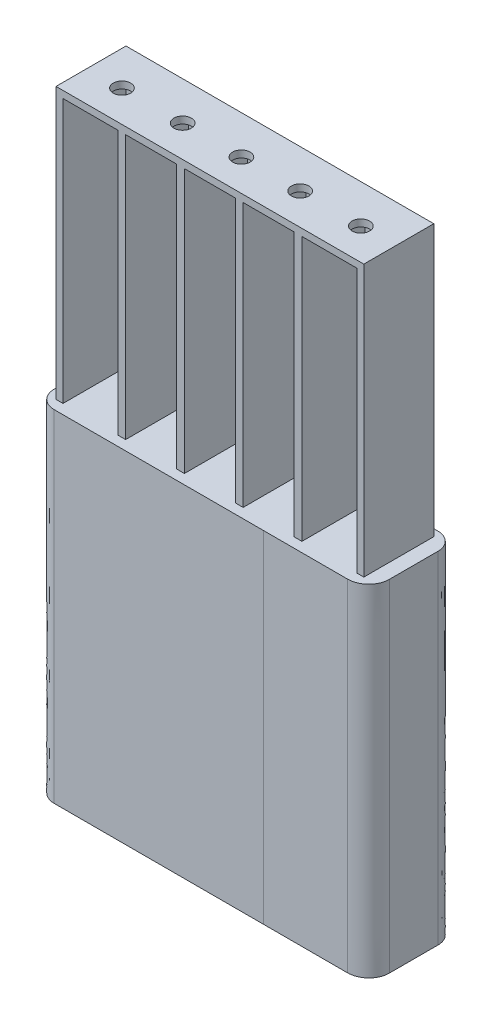
SolidWorks part; units mm, degrees
ref_plane "Front Plane" through (0, 0, 0) normal (0, 0, 1) x (1, 0, 0)
ref_plane "Top Plane" through (0, 0, 0) normal (0, 1, 0) x (1, 0, 0)
ref_plane "Right Plane" through (0, 0, 0) normal (1, 0, 0) x (0, 0, -1)
ref_plane "Plane1" through (0, 10, 0) normal (0, 1, 0) x (1, 0, 0)
sketch "Sketch1" plane through (0, 0, 0) normal (0, 0, 1) x (1, 0, 0)
  line L1 (-44, -87.5) -> (44, -87.5)
  line L2 (-44, -87.5) -> (-44, 87.5)
  line L3 (-44, 87.5) -> (44, 87.5)
  line L4 (44, -87.5) -> (44, 87.5)
  line L5 (-44, -87.5) -> (44, 87.5) construction
  line L6 (-44, 87.5) -> (44, -87.5) construction
  point P0 (0, 0)
  dimension "D1" = 88
  dimension "D2" = 175
extrude "Boss-Extrude1" add sketch "Sketch1" along normal blind 2
sketch "Sketch2" plane through (0, 0, 2) normal (0, 0, 1) x (1, 0, 0)
  line L4 (44, -87.5) -> (44, 87.5)
  line L5 (44, 87.5) -> (-44, 87.5)
  line L6 (-44, 87.5) -> (-44, -87.5)
  line L7 (-44, -87.5) -> (44, -87.5)
  line L8 (44, -87.5) -> (44, 87.5)
  line L9 (44, 87.5) -> (-44, 87.5)
  line L10 (-44, 87.5) -> (-44, -87.5)
  line L11 (-44, -87.5) -> (44, -87.5)
  dimension "D1" = 0
extrude "Extrude-Thin1" add sketch "Sketch2" along normal blind 18 thin thin type one direction reverse wall 2
sketch "Sketch3" plane through (0, 0, 2) normal (0, 0, 1) x (1, 0, 0)
  line L0 (-25.2, 85.5) -> (-25.2, -85.5)
  line L1 (42, 85.5) -> (-42, 85.5) construction
  line L2 (-42, -85.5) -> (42, -85.5) construction
  line L3 (-8.4, 85.5) -> (-8.4, -85.5)
  line L4 (42, 85.5) -> (-42, 85.5) construction
  line L5 (25.2, 85.5) -> (25.2, -85.5)
  line L6 (8.4, 85.5) -> (8.4, -85.5)
  line L7 (-42, -85.5) -> (42, -85.5) construction
  line L8 (-42, 85.5) -> (-42, -85.5) construction
  line L9 (42, -85.5) -> (42, 85.5) construction
  dimension "D1" = 16.8
  dimension "D2" = 16.8
  dimension "D3" = 16.8
  dimension "D4" = 16.8
  dimension "D5" = 16.8
extrude "Extrude-Thin2" add sketch "Sketch3" along normal blind 18 thin thin type mid plane wall 2.2
sketch "Sketch4" plane through (0, 87.5, 0) normal (0, 1, 0) x (1, 0, 0)
  line L0 (26.3, -20) -> (26.3, -2) construction
  line L1 (26.3, -2) -> (42, -2) construction
  line L2 (42, -2) -> (42, -20) construction
  line L3 (42, -20) -> (26.3, -20) construction
  line L4 (9.5, -20) -> (9.5, -2) construction
  line L5 (9.5, -2) -> (24.1, -2) construction
  line L6 (24.1, -2) -> (24.1, -20) construction
  line L7 (24.1, -20) -> (9.5, -20) construction
  line L8 (-7.3, -2) -> (7.3, -2) construction
  line L9 (7.3, -2) -> (7.3, -20) construction
  line L10 (7.3, -20) -> (-7.3, -20) construction
  line L11 (-7.3, -20) -> (-7.3, -2) construction
  line L12 (-24.1, -2) -> (-9.5, -2) construction
  line L13 (-9.5, -2) -> (-9.5, -20) construction
  line L14 (-9.5, -20) -> (-24.1, -20) construction
  line L15 (-24.1, -20) -> (-24.1, -2) construction
  line L16 (-42, -2) -> (-26.3, -2) construction
  line L17 (-26.3, -2) -> (-26.3, -20) construction
  line L18 (-26.3, -20) -> (-42, -20) construction
  line L19 (-42, -20) -> (-42, -2) construction
  line L20 (26.3, -20) -> (26.3, -2) construction
  line L21 (26.3, -2) -> (42, -2) construction
  line L22 (42, -2) -> (42, -20) construction
  line L23 (42, -20) -> (26.3, -20) construction
  line L24 (9.5, -20) -> (9.5, -2) construction
  line L25 (9.5, -2) -> (24.1, -2) construction
  line L26 (24.1, -2) -> (24.1, -20) construction
  line L27 (24.1, -20) -> (9.5, -20) construction
  line L28 (-7.3, -2) -> (7.3, -2) construction
  line L29 (7.3, -2) -> (7.3, -20) construction
  line L30 (7.3, -20) -> (-7.3, -20) construction
  line L31 (-7.3, -20) -> (-7.3, -2) construction
  line L32 (-24.1, -2) -> (-9.5, -2) construction
  line L33 (-9.5, -2) -> (-9.5, -20) construction
  line L34 (-9.5, -20) -> (-24.1, -20) construction
  line L35 (-24.1, -20) -> (-24.1, -2) construction
  line L36 (-42, -2) -> (-26.3, -2) construction
  line L37 (-26.3, -2) -> (-26.3, -20) construction
  line L38 (-26.3, -20) -> (-42, -20) construction
  line L39 (-42, -20) -> (-42, -2) construction
  line L40 (42, -11) -> (-42, -11) construction
  line L41 (-16.8, -20) -> (-16.8, -2) construction
  line L42 (-34.15, -20) -> (-34.15, -2) construction
  line L43 (0, -20) -> (0, -2) construction
  line L44 (16.8, -20) -> (16.8, -2) construction
  line L45 (34.15, -20) -> (34.15, -2) construction
  point P26 (34.15, -11)
  point P28 (16.8, -11)
  point P30 (0, -11)
  point P31 (-16.8, -11)
  point P34 (-34.15, -11)
hole_wizard "Ø5.0mm Dowel Hole3" positions "Sketch5" profile "Sketch6" hole size "Ø5.0" standard "BSI" end condition up to next
sketch "Sketch5" plane through (0, 87.5, 0) normal (0, 1, 0) x (1, 0, 0)
  line L0 (-34.15, -20) -> (-34.15, -2) construction
  line L1 (-16.8, -20) -> (-16.8, -2) construction
  point P0 (-34.15, -11)
  point P4 (-16.8, -11)
  point P8 (0, -11)
  point P11 (16.8, -11)
  point P14 (34.15, -11)
sketch "Sketch6" plane through (-34.15, 87.5, 11) normal (1, 0, 0) x (0, 0, 1)
  line L0 (0, 0) -> (0, 2)
  line L1 (0, 2) -> (2.5, 2)
  line L2 (2.5, 2) -> (2.5, 0)
  line L5 (2.5, 0) -> (0, 0)
  line L11 (0, -6.35) -> (0, 107.95) construction
  dimension "Thru Hole Dia." = 5
  dimension "Thru Hole Depth" = 2
sketch "Sketch7" plane through (0, 10, 0) normal (0, -1, 0) x (1, 0, 0)
  line L5 (-41.7947, -2) -> (43.1333, -2)
  line L6 (48.2045, 2.9357) -> (48.2045, 16.9113)
  line L7 (42.125, 22.8183) -> (18.1019, 22.8081)
  line L8 (18.1019, 22.8081) -> (-41.7556, 22.7981)
  line L9 (-46.7955, 17.7993) -> (-46.7955, 2.97)
  line L10 (-41.7947, -2) -> (43.1333, -2)
  line L11 (48.2045, 2.9357) -> (48.2045, 16.9113)
  line L12 (42.125, 22.8183) -> (18.1019, 22.8081)
  line L13 (18.1019, 22.8081) -> (-41.7556, 22.7981)
  line L14 (-46.7955, 17.7993) -> (-46.7955, 2.97)
  spline S4 degree 3 poles (-570.9003, 2933.4102) (-107.6678, 422.5311) (5.2194, -9.2538) (44.4297, -1.8483) (44.748, -1.7568) (45.359, -1.5153) (45.6493, -1.3671) (46.1994, -1.0159) (46.4616, -0.8102) (46.9336, -0.3574) (47.1455, -0.1099) (47.4262, 0.2936) (47.514, 0.4343) (47.6737, 0.7219) (47.7457, 0.8688) (47.9389, 1.3182) (48.0374, 1.6296) (57.1044, 45.5515) (-540.3307, 163.4471) (-1639.0805, -2413.0024) knots -15.05146 -15.05146 -15.05146 -15.05146 0.125 0.125 0.25 0.25 0.375 0.375 0.5 0.5 0.625 0.625 0.6875 0.6875 0.75 0.75 0.875 0.875 17.709186 17.709186 17.709186 17.709186 only from (43.1333, -2) to (48.2045, 2.9357)
  spline S5 degree 3 poles (-2884.0595, -611.2323) (-408.613, -147.3192) (56.7555, -24.4102) (48.0477, 18.2712) (47.9989, 18.461) (47.8815, 18.8372) (47.8126, 19.0236) (47.5808, 19.5649) (47.3916, 19.9066) (47.0561, 20.3904) (46.9348, 20.5478) (46.6788, 20.8475) (46.5441, 20.9899) (46.1207, 21.3956) (45.8129, 21.6376) (45.1451, 22.0633) (44.7957, 22.2403) (44.0682, 22.5266) (43.6865, 22.6364) (-19.83, 34.5783) (-199.7643, -921.786) (-505.9701, -2924.8562) knots -13.746336 -13.746336 -13.746336 -13.746336 0.125 0.125 0.1875 0.1875 0.25 0.25 0.375 0.375 0.4375 0.4375 0.5 0.5 0.625 0.625 0.75 0.75 0.875 0.875 21.26105 21.26105 21.26105 21.26105 only from (48.2045, 16.9113) to (42.125, 22.8183)
  spline S6 degree 3 poles (567.701, -2913.6183) (94.7522, -349.5417) (-6.8251, 29.7465) (-42.894, 22.6717) (-43.053, 22.6324) (-43.3684, 22.5381) (-43.5253, 22.4827) (-43.982, 22.2959) (-44.271, 22.1434) (-44.8182, 21.7829) (-45.0779, 21.5726) (-45.5439, 21.1126) (-45.7531, 20.8616) (-46.0304, 20.4526) (-46.1168, 20.3104) (-46.2734, 20.0213) (-46.3441, 19.8738) (-46.534, 19.422) (-46.6314, 19.1076) (-56.8249, -31.2707) (712.2955, -165.4521) (2914.5191, -454.3512) knots -13.870589 -13.870589 -13.870589 -13.870589 0.125 0.125 0.1875 0.1875 0.25 0.25 0.375 0.375 0.5 0.5 0.625 0.625 0.6875 0.6875 0.75 0.75 0.875 0.875 20.162179 20.162179 20.162179 20.162179 only from (-41.7556, 22.7981) to (-46.7955, 17.7993)
  spline S7 degree 3 poles (2889.4301, 613.265) (340.3527, 142.5545) (-53.9089, 38.1525) (-46.6679, 1.8393) (-46.6283, 1.6814) (-46.5331, 1.3683) (-46.4771, 1.2127) (-46.2887, 0.7605) (-46.1349, 0.4746) (-45.7714, -0.0662) (-45.5599, -0.3219) (-45.0982, -0.7797) (-44.8463, -0.985) (-44.2993, -1.3471) (-44.009, -1.5004) (-43.4082, -1.7468) (-43.0937, -1.8415) (9.2099, -12.1359) (154.4436, 801.6988) (451.3448, 2955.8147) knots -14.064879 -14.064879 -14.064879 -14.064879 0.125 0.125 0.1875 0.1875 0.25 0.25 0.375 0.375 0.5 0.5 0.625 0.625 0.75 0.75 0.875 0.875 21.050483 21.050483 21.050483 21.050483 only from (-46.7955, 2.97) to (-41.7947, -2)
  spline S8 degree 3 poles (43.1333, -2) (43.4638, -2) (43.7891, -1.9693) (44.4297, -1.8483) (44.748, -1.7568) (45.359, -1.5153) (45.6493, -1.3671) (46.1994, -1.0159) (46.4616, -0.8102) (46.9336, -0.3574) (47.1455, -0.1099) (47.4262, 0.2936) (47.514, 0.4343) (47.6737, 0.7219) (47.7457, 0.8688) (47.9389, 1.3182) (48.0374, 1.6296) (48.1711, 2.2771) (48.2045, 2.6049) (48.2045, 2.9357) knots 0 0 0 0 0.125 0.125 0.25 0.25 0.375 0.375 0.5 0.5 0.625 0.625 0.6875 0.6875 0.75 0.75 0.875 0.875 1 1 1 1
  spline S9 degree 3 poles (48.2045, 16.9113) (48.2045, 17.3074) (48.1648, 17.6968) (48.0477, 18.2712) (47.9989, 18.461) (47.8815, 18.8372) (47.8126, 19.0236) (47.5808, 19.5649) (47.3916, 19.9066) (47.0561, 20.3904) (46.9348, 20.5478) (46.6788, 20.8475) (46.5441, 20.9899) (46.1207, 21.3956) (45.8129, 21.6376) (45.1451, 22.0633) (44.7957, 22.2403) (44.0682, 22.5266) (43.6865, 22.6364) (42.9123, 22.7819) (42.5209, 22.8183) (42.125, 22.8183) knots 0 0 0 0 0.125 0.125 0.1875 0.1875 0.25 0.25 0.375 0.375 0.4375 0.4375 0.5 0.5 0.625 0.625 0.75 0.75 0.875 0.875 1 1 1 1
  spline S10 degree 3 poles (-41.7556, 22.7981) (-42.087, 22.7981) (-42.4129, 22.766) (-42.894, 22.6717) (-43.053, 22.6324) (-43.3684, 22.5381) (-43.5253, 22.4827) (-43.982, 22.2959) (-44.271, 22.1434) (-44.8182, 21.7829) (-45.0779, 21.5726) (-45.5439, 21.1126) (-45.7531, 20.8616) (-46.0304, 20.4526) (-46.1168, 20.3104) (-46.2734, 20.0213) (-46.3441, 19.8738) (-46.534, 19.422) (-46.6314, 19.1076) (-46.7626, 18.4588) (-46.7955, 18.1308) (-46.7955, 17.7993) knots 0 0 0 0 0.125 0.125 0.1875 0.1875 0.25 0.25 0.375 0.375 0.5 0.5 0.625 0.625 0.6875 0.6875 0.75 0.75 0.875 0.875 1 1 1 1
  spline S11 degree 3 poles (-46.7955, 2.97) (-46.7955, 2.6408) (-46.7632, 2.317) (-46.6679, 1.8393) (-46.6283, 1.6814) (-46.5331, 1.3683) (-46.4771, 1.2127) (-46.2887, 0.7605) (-46.1349, 0.4746) (-45.7714, -0.0662) (-45.5599, -0.3219) (-45.0982, -0.7797) (-44.8463, -0.985) (-44.2993, -1.3471) (-44.009, -1.5004) (-43.4082, -1.7468) (-43.0937, -1.8415) (-42.4496, -1.9682) (-42.1239, -2) (-41.7947, -2) knots 0 0 0 0 0.125 0.125 0.1875 0.1875 0.25 0.25 0.375 0.375 0.5 0.5 0.625 0.625 0.75 0.75 0.875 0.875 1 1 1 1
  dimension "D1" = 0
extrude "Boss-Extrude2" add sketch "Sketch7" along normal up to surface (97.5 mm away) up to face at (0, -87.5, 10)
